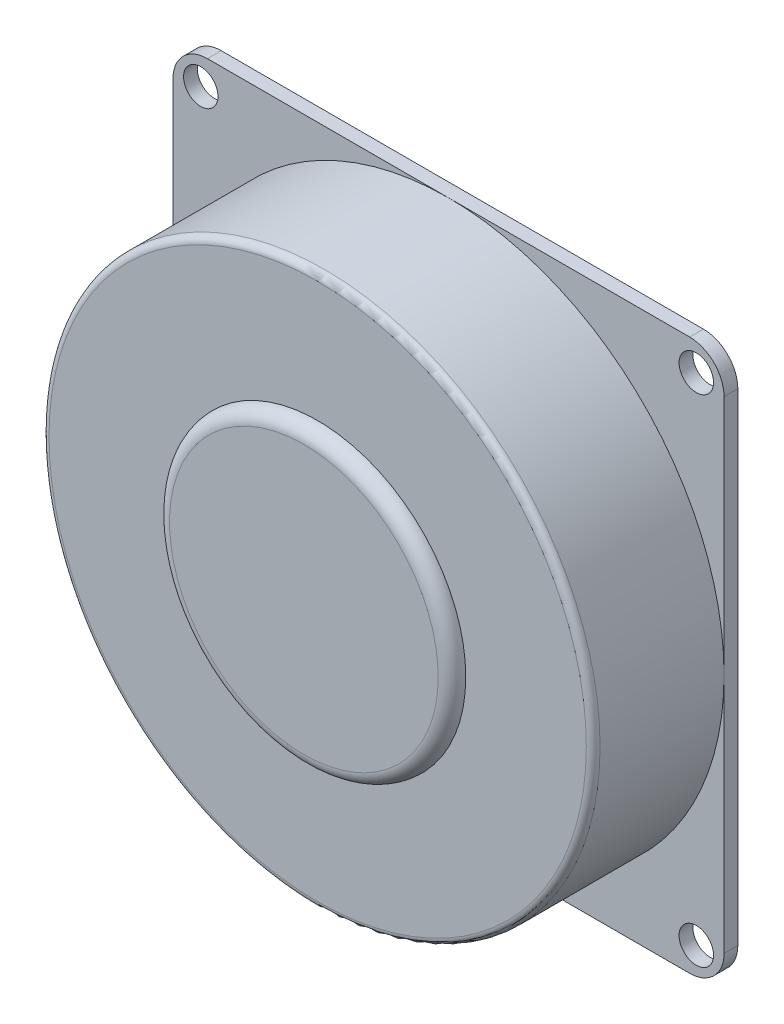
SolidWorks part; units mm, degrees
ref_plane "Plan de face" through (0, 0, 0) normal (0, 0, 1) x (1, 0, 0)
ref_plane "Plan de dessus" through (0, 0, 0) normal (0, 1, 0) x (1, 0, 0)
ref_plane "Plan de droite" through (0, 0, 0) normal (1, 0, 0) x (0, 0, -1)
sketch "Esquisse1" plane through (0, 0, 0) normal (0, 0, 1) x (1, 0, 0)
  line L0 (5.6337, 33.7844) -> (5.6337, -46.2156) construction
  line L1 (-34.3663, 33.7844) -> (45.6337, 33.7844)
  line L2 (-34.3663, 33.7844) -> (-34.3663, -46.2156)
  line L3 (-34.3663, -46.2156) -> (45.6337, -46.2156)
  line L4 (45.6337, 33.7844) -> (45.6337, -46.2156)
  circle A0 centre (-30.3376, 29.7844) radius 2.5
  circle A1 centre (-30.3376, -42.2156) radius 2.5
  circle A2 centre (41.6049, -42.2156) radius 2.5
  circle A3 centre (41.6049, 29.7844) radius 2.5
  dimension "D3" = 5
  dimension "D1" = 80
  dimension "D2" = 80
  dimension "D4" = 2
  dimension "D5" = 72
  dimension "D6" = 4
extrude "Boss.-Extru.1" add sketch "Esquisse1" along normal blind 2
sketch "Esquisse2" plane through (0, 0, 2) normal (0, 0, 1) x (1, 0, 0)
  circle A0 centre (5.6337, -6.2156) radius 40
extrude "Boss.-Extru.2" add sketch "Esquisse2" along normal blind 19
sketch "Esquisse3" plane through (0, 0, 21) normal (0, 0, 1) x (1, 0, 0)
  circle A0 centre (5.6337, -6.2156) radius 21.5
  dimension "D1" = 43
extrude "Boss.-Extru.3" add sketch "Esquisse3" along normal blind 2
fillet "Congé1" radius 5 4 edges at (45.6337, -46.2156, 1) (-34.3663, -46.2156, 1) (45.6337, 33.7844, 1) (-34.3663, 33.7844, 1)
fillet "Congé2" radius 2 1 edges at (27.1337, -6.2156, 23)
fillet "Congé3" radius 1 1 edges at (45.6337, -6.2156, 21)
